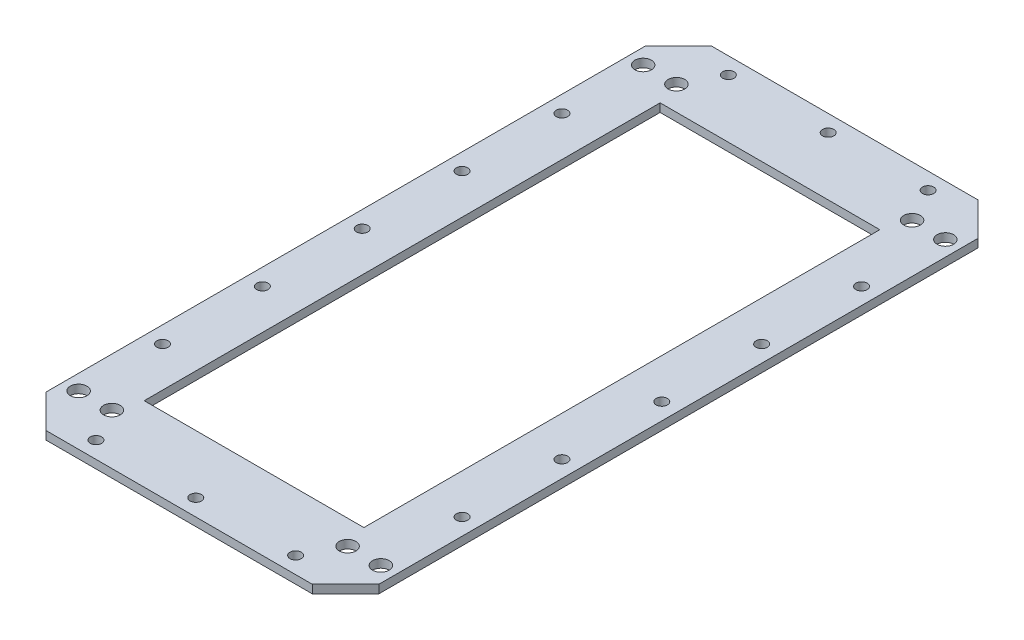
SolidWorks part; units mm, degrees
ref_plane "Front Plane" through (0, 0, 0) normal (0, 0, 1) x (1, 0, 0)
ref_plane "Top Plane" through (0, 0, 0) normal (0, 1, 0) x (1, 0, 0)
ref_plane "Right Plane" through (0, 0, 0) normal (1, 0, 0) x (0, 0, -1)
sketch "Sketch2" plane through (0, 0, 0) normal (0, 1, 0) x (1, 0, 0)
  line L0 (0, 12.7) -> (0, 241.3)
  line L1 (12.7, 254) -> (114.3, 254)
  line L2 (127, 241.3) -> (127, 12.7)
  line L3 (114.3, 0) -> (12.7, 0)
  line L4 (0, 241.3) -> (12.7, 254)
  line L5 (114.3, 254) -> (127, 241.3)
  line L6 (127, 12.7) -> (114.3, 0)
  line L7 (12.7, 0) -> (0, 12.7)
  line L8 (63.5, 254) -> (63.5, -20.3774) construction
  line L10 (0, 127) -> (136.1553, 127) construction
  line L11 (21.59, 225.425) -> (105.41, 225.425)
  line L12 (21.59, 225.425) -> (21.59, 28.575)
  line L13 (21.59, 28.575) -> (105.41, 28.575)
  line L14 (105.41, 225.425) -> (105.41, 28.575)
  line L17 (21.59, 225.425) -> (105.41, 28.575) construction
  line L18 (21.59, 28.575) -> (105.41, 225.425) construction
  circle A1 centre (6.35, 165.1) radius 2.159
  circle A13 centre (25.4, 247.65) radius 2.159
  circle A42 centre (6.35, 203.2) radius 2.159
  circle A43 centre (63.5, 247.65) radius 2.159
  circle A46 centre (6.35, 127) radius 2.159
  circle A56 centre (120.65, 127) radius 2.159
  circle A57 centre (120.65, 165.1) radius 2.159
  circle A58 centre (120.65, 203.2) radius 2.159
  circle A59 centre (101.6, 247.65) radius 2.159
  circle A60 centre (101.6, 6.35) radius 2.159
  circle A61 centre (63.5, 6.35) radius 2.159
  circle A62 centre (25.4, 6.35) radius 2.159
  circle A63 centre (120.65, 50.8) radius 2.159
  circle A64 centre (6.35, 50.8) radius 2.159
  circle A65 centre (120.65, 88.9) radius 2.159
  circle A66 centre (6.35, 88.9) radius 2.159
  point P0 (63.5, 127)
  point P37 (127, 127)
  point P42 (63.5, 0)
  dimension "D8" = 28.575
  dimension "D9" = 21.59
  dimension "D14" = 101.6
  dimension "D16" = 12.7
  dimension "D17" = 254
  dimension "D22" = 228.6
  dimension "D24" = 38.1
  dimension "D30" = 38.1
  dimension "D32" = 4.318
  dimension "D33" = 4.318
  dimension "D36" = 101.6
  dimension "D37" = 228.6
  dimension "D44" = 4.318
  dimension "D45" = 6.35
  dimension "D49" = 4.318
  dimension "D50" = 4.318
  dimension "D51" = 6.35
  dimension "D7" = 127
  dimension "D15" = 12.7
  dimension "D67" = 38.1
extrude "Boss-Extrude1" add sketch "Sketch2" along normal blind 3.175 contours L7 L3 L6 L2 L5 L1 L4 L0 A46 A66 A43 A42 A64 A13 A59 A56 region at (2.8398, 0, -127)
sketch "Sketch3" plane through (0, 3.175, 0) normal (0, 1, 0) x (1, 0, 0)
  line L0 (63.5, 254) -> (63.5, 0) construction
  line L1 (12.7, 254) -> (114.3, 254) construction
  line L2 (114.3, 0) -> (12.7, 0) construction
  line L3 (0, 127) -> (127, 127) construction
  line L4 (0, 12.7) -> (0, 241.3) construction
  line L5 (127, 241.3) -> (127, 12.7) construction
  circle A0 centre (5.842, 234.696) radius 3.175
  circle A1 centre (18.542, 234.696) radius 3.175
  circle A2 centre (108.458, 234.696) radius 3.175
  circle A3 centre (121.158, 234.696) radius 3.175
  circle A4 centre (121.158, 19.304) radius 3.175
  circle A5 centre (108.458, 19.304) radius 3.175
  circle A6 centre (18.542, 19.304) radius 3.175
  circle A7 centre (5.842, 19.304) radius 3.175
  point P16 (0, 0)
  dimension "D1" = 6.35
  dimension "D2" = 6.35
  dimension "D3" = 19.304
  dimension "D4" = 5.842
  dimension "D5" = 18.542
extrude "Cut-Extrude1" cut sketch "Sketch3" against normal through all
